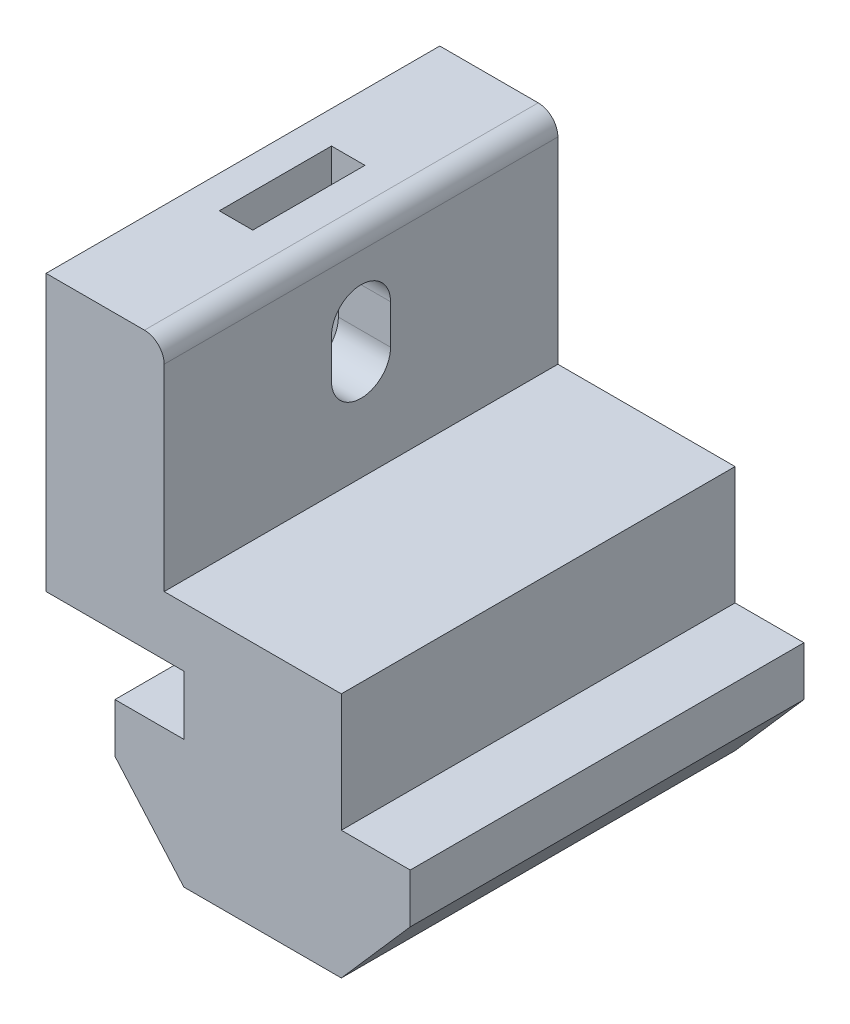
SolidWorks part; units mm, degrees
ref_plane "Piano frontale" through (0, 0, 0) normal (0, 0, 1) x (1, 0, 0)
ref_plane "Piano superiore" through (0, 0, 0) normal (0, 1, 0) x (1, 0, 0)
ref_plane "Piano destro" through (0, 0, 0) normal (1, 0, 0) x (0, 0, -1)
sketch "Schizzo2" plane through (0, 0, 0) normal (0, 0, 1) x (1, 0, 0)
  line L0 (0, 0) -> (0, 12.9875) construction
  line L1 (-4, 9.5) -> (-11, 9.5)
  line L2 (-11, 9.5) -> (-11, 23.5)
  line L3 (-11, 23.5) -> (-6, 23.5)
  line L4 (-5, 22.5) -> (-5, 12.5)
  line L5 (-5, 12.5) -> (4, 12.5)
  line L6 (4, 12.5) -> (4, 9.5)
  line L13 (-4, 0) -> (4, 0)
  line L14 (-7.5, 4) -> (-4, 0)
  line L15 (-7.5, 6.5) -> (-7.5, 4)
  line L16 (-4, 6.5) -> (-7.5, 6.5)
  line L17 (-4, 9.5) -> (-4, 6.5)
  line L44 (7.5, 4) -> (4, 0)
  line L45 (7.5, 6.5) -> (7.5, 4)
  line L46 (4, 6.5) -> (7.5, 6.5)
  line L72 (4, 9.5) -> (4, 6.5)
  arc A0 (-6, 23.5) -> (-5, 22.5) centre (-6, 22.5) cw
  point P9 (-5, 23.5)
  dimension "D11" = 1
  dimension "D1" = 8
  dimension "D2" = 4
  dimension "D3" = 2.5
  dimension "D4" = 8
  dimension "D5" = 3
  dimension "D6" = 15
  dimension "D7" = 11
  dimension "D8" = 6
  dimension "D9" = 3
  dimension "D10" = 14
extrude "Estrusione-Estrusione1" add sketch "Schizzo2" against normal blind 20
sketch "Schizzo6" plane through (-11, 0, 0) normal (-1, 0, 0) x (0, 0, 1)
  line L0 (0, 23.5) -> (0, 9.5) construction
  line L1 (-20, 23.5) -> (0, 23.5) construction
  line L2 (-10, 19.5) -> (-10, 17.5) construction
  line L3 (-8.5, 19.5) -> (-8.5, 17.5)
  line L4 (-11.5, 19.5) -> (-11.5, 17.5)
  line L5 (-20, 9.5) -> (0, 9.5) construction
  arc A1 (-8.5, 19.5) -> (-11.5, 19.5) centre (-10, 19.5) ccw
  arc A2 (-11.5, 17.5) -> (-8.5, 17.5) centre (-10, 17.5) ccw
  point P6 (-10, 18.5)
  dimension "D2" = 1.5
  dimension "D1" = 10
  dimension "D3" = 4
  dimension "D4" = 2
  dimension "D5" = 9
extrude "Taglio-Estrusione1" cut sketch "Schizzo6" against normal up to next
sketch "Schizzo11" plane through (0, 0, -20) normal (0, 0, -1) x (-1, 0, 0)
  line L0 (4, 0) -> (-4, 0) construction
  line L1 (7.5, 6.5) -> (7.5, 4) construction
  text T0 "3" font "Century Gothic" height 6.5
  dimension "D1" = 1
  dimension "D2" = 10.5
extrude "Estrusione-Estrusione4" add sketch "Schizzo11" along normal blind 0.6
sketch "Schizzo12" plane through (0, 23.5, 0) normal (0, 1, 0) x (1, 0, 0)
  line L0 (-6, 10) -> (-11, 10) construction
  line L1 (-6, 20) -> (-6, 0) construction
  line L2 (-11, 20) -> (-11, 0) construction
  line L4 (-7.65, 7.15) -> (-9.35, 7.15)
  line L5 (-7.65, 7.15) -> (-7.65, 12.85)
  line L6 (-7.65, 12.85) -> (-9.35, 12.85)
  line L7 (-9.35, 7.15) -> (-9.35, 12.85)
  line L8 (-7.65, 7.15) -> (-9.35, 12.85) construction
  line L9 (-7.65, 12.85) -> (-9.35, 7.15) construction
  point P6 (-8.5, 10)
  dimension "D1" = 1.7
  dimension "D2" = 5.7
extrude "Taglio-Estrusione2" cut sketch "Schizzo12" against normal blind 10
